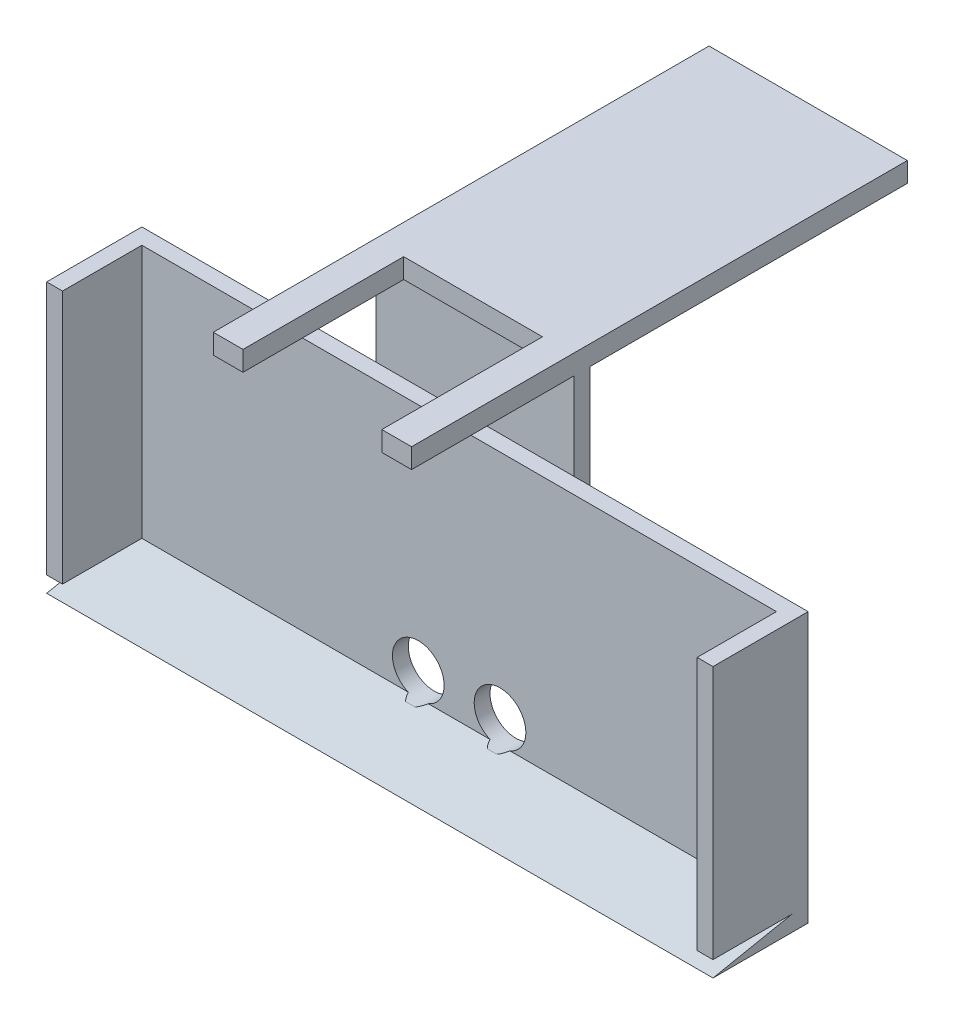
SolidWorks part; units mm, degrees
material "ABS"
ref_plane "Front Plane" through (0, 0, 0) normal (0, 0, 1) x (1, 0, 0)
ref_plane "Top Plane" through (0, 0, 0) normal (0, 1, 0) x (1, 0, 0)
ref_plane "Right Plane" through (0, 0, 0) normal (1, 0, 0) x (0, 0, -1)
sketch "Sketch1" plane through (0, 0, 0) normal (0, 1, 0) x (1, 0, 0)
  line L1 (-101.6, -12.7) -> (101.6, -12.7)
  line L2 (-101.6, -12.7) -> (-101.6, 12.7)
  line L3 (-101.6, 12.7) -> (101.6, 12.7)
  line L4 (101.6, -12.7) -> (101.6, 12.7)
  line L5 (-101.6, -12.7) -> (101.6, 12.7) construction
  line L6 (-101.6, 12.7) -> (101.6, -12.7) construction
  point P0 (0, 0)
  dimension "D1" = 203.2
extrude "Boss-Extrude1" add sketch "Sketch1" along normal blind 5.08 contours L3 L4 L1 L2
ref_plane "Plane1" through (0, 0, 0) normal (1, 0, 0) x (0, 0, -1)
ref_plane "Plane2" through (101.6, 0, 0) normal (1, 0, 0) x (0, 0, -1)
sketch "Sketch4" plane through (101.6, 0, 0) normal (1, 0, 0) x (0, 0, -1)
  line L0 (-12.7, 0) -> (-12.7, 5.08)
  line L1 (-12.7, 5.08) -> (-12.7, 86.36)
  line L2 (-12.7, 86.36) -> (12.7, 86.36)
  line L3 (12.7, 86.36) -> (12.7, 5.08)
  line L4 (12.7, 5.08) -> (12.7, 0)
  line L5 (12.7, 0) -> (-12.7, 0)
extrude "Boss-Extrude2" add sketch "Sketch4" along normal blind 5.08
mirror "Mirror1" about plane through (0, 0, 0) normal (1, 0, 0) of "Boss-Extrude2"
sketch "Sketch5" plane through (0, 0, -12.7) normal (0, 0, -1) x (-1, 0, 0)
  line L1 (-106.68, 86.36) -> (106.68, 86.36)
  line L2 (-106.68, 86.36) -> (-106.68, 0)
  line L3 (-106.68, 0) -> (106.68, 0)
  line L4 (106.68, 86.36) -> (106.68, 0)
extrude "Boss-Extrude3" add sketch "Sketch5" along normal blind 5.08
sketch "Sketch6" plane through (106.68, 0, 0) normal (1, 0, 0) x (0, 0, -1)
  line L0 (-12.7, 0) -> (12.7, 5.08)
  line L4 (12.7, 5.08) -> (-12.7, 5.08)
  line L5 (-12.7, 86.36) -> (-12.7, 0) construction
  line L6 (-12.7, 5.08) -> (-12.7, 0)
  line L7 (-12.7, 0) -> (17.78, 0) construction
  line L8 (17.78, 86.36) -> (17.78, 0) construction
  line L9 (-12.7, 5.08) -> (12.7, 5.08) construction
  dimension "D1" = 5.08
extrude "Cut-Extrude2" cut sketch "Sketch6" against normal through all contours L4 L6 L0
sketch "Sketch7" plane through (0, 0, -17.78) normal (0, 0, -1) x (-1, 0, 0)
  line L0 (-31.75, 50.8) -> (31.75, 50.8)
  line L1 (-106.68, 0) -> (106.68, 0) construction
  line L2 (-31.75, 50.8) -> (-31.75, 114.3)
  line L3 (-31.75, 114.3) -> (31.75, 114.3)
  line L4 (31.75, 114.3) -> (31.75, 50.8)
  point P3 (0, 50.8)
  dimension "D1" = 50.8
  dimension "D2" = 63.5
extrude "Boss-Extrude4" add sketch "Sketch7" along normal blind 5.08 contours L2 L3 L4 L0
sketch "Sketch8" plane through (0, 114.3, 0) normal (0, 1, 0) x (1, 0, 0)
  line L0 (-31.75, 22.86) -> (-31.75, 124.46)
  line L1 (-31.75, 22.86) -> (-31.75, 17.78)
  line L2 (-31.75, 17.78) -> (-31.75, -34.2815)
  line L3 (-31.75, -34.2815) -> (31.75, -34.2815)
  line L4 (31.75, -34.2815) -> (31.75, 17.78)
  line L5 (31.75, 17.78) -> (31.75, 22.86)
  line L6 (31.75, 22.86) -> (31.75, 124.46)
  line L7 (31.75, 124.46) -> (-31.75, 124.46)
  dimension "D1" = 101.6
extrude "Boss-Extrude5" add sketch "Sketch8" along normal blind 6.35
sketch "Sketch9" plane through (0, 120.65, 0) normal (0, 1, 0) x (1, 0, 0)
  line L1 (22.225, -41.1636) -> (-22.225, -41.1636)
  line L2 (22.225, -41.1636) -> (22.225, 17.1614)
  line L3 (22.225, 17.1614) -> (-22.225, 17.1614)
  line L4 (-22.225, -41.1636) -> (-22.225, 17.1614)
  point P0 (0, 0)
extrude "Cut-Extrude3" cut sketch "Sketch9" against normal up to next contours L3 L4 L1 L2
sketch "Sketch10" plane through (0, 0, -12.7) normal (0, 0, 1) x (1, 0, 0)
  line L0 (-13.081, 12.7) -> (13.081, 12.7) construction
  line L1 (-106.68, 0) -> (106.68, 0) construction
  circle A0 centre (-13.081, 12.7) radius 8.2697
  circle A1 centre (13.081, 12.7) radius 8.2697
  point P3 (0, 12.7)
  point P7 (-13.4781, 12.7)
  point P8 (0, 0)
  dimension "D1" = 12.7
extrude "Cut-Extrude4" cut sketch "Sketch10" against normal through all and the other way blind 2.54
